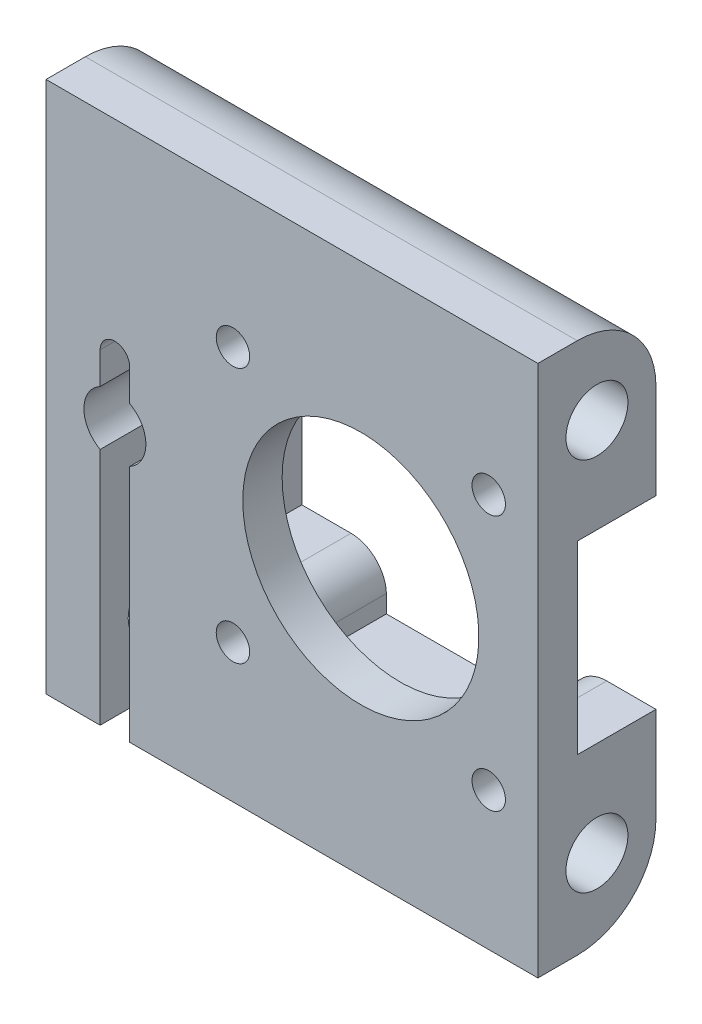
SolidWorks part; units mm, degrees
ref_plane "Front Plane" through (0, 0, 0) normal (0, 0, 1) x (1, 0, 0)
ref_plane "Top Plane" through (0, 0, 0) normal (0, 1, 0) x (1, 0, 0)
ref_plane "Right Plane" through (0, 0, 0) normal (1, 0, 0) x (0, 0, -1)
sketch "Sketch1" plane through (0, 0, 0) normal (0, 0, 1) x (1, 0, 0)
  line L1 (0, 0) -> (50, 0)
  line L2 (0, 0) -> (0, 54.105)
  line L3 (0, 54.105) -> (50, 54.105)
  line L4 (50, 0) -> (50, 54.105)
  dimension "D1" = 54.105
  dimension "D2" = 50
extrude "Boss-Extrude1" add sketch "Sketch1" along normal blind 12
sketch "Sketch2" plane through (0, 0, 0) normal (1, 0, 0) x (0, 0, -1)
  line L0 (-12, 27.0525) -> (0, 27.0525) construction
  line L1 (-12, 0) -> (-12, 54.105) construction
  line L2 (0, 0) -> (0, 54.105) construction
  circle A0 centre (-6, 46.105) radius 3.15
  circle A1 centre (-6, 8) radius 3.15
  dimension "D2" = 6.3
  dimension "D1" = 6
  dimension "D3" = 19.0525
extrude "Cut-Extrude1" cut sketch "Sketch2" along normal through all
fillet "Fillet1" radius 8 2 edges at (25, 0, 0) (25, 54.105, 0)
sketch "Sketch3" plane through (0, 0, 0) normal (0, 0, -1) x (-1, 0, 0)
  line L0 (-50, 27.0525) -> (0, 27.0525) construction
  line L1 (-50, 8) -> (-50, 46.105) construction
  line L2 (0, 46.105) -> (0, 8) construction
  line L3 (-8.5, 0) -> (-8.5, 24.2826)
  line L5 (-5.5, 33.0525) -> (-5.5, 29.8224)
  line L6 (0, 0) -> (-50, 0) construction
  line L7 (-8.5, 0) -> (-5.5, 0)
  line L8 (-8.5, 29.8224) -> (-8.5, 33.0525)
  line L9 (-5.5, 24.2826) -> (-5.5, 0)
  arc A0 (-8.5, 29.8224) -> (-8.5, 24.2826) centre (-7, 27.0525) ccw
  circle A1 centre (-32, 27.0525) radius 12
  circle A2 centre (-19, 40.0525) radius 1.7
  circle A3 centre (-19, 14.0525) radius 1.7
  arc A4 (-5.5, 24.2826) -> (-5.5, 29.8224) centre (-7, 27.0525) ccw
  arc A5 (-5.5, 33.0525) -> (-8.5, 33.0525) centre (-7, 33.0525) ccw
  circle A6 centre (-45, 14.0525) radius 1.7
  circle A7 centre (-45, 40.0525) radius 1.7
  dimension "D1" = 24
  dimension "D2" = 6.3
  dimension "D5" = 3.4
  dimension "D6" = 1.5
  dimension "D7" = 13
  dimension "D10" = 13
  dimension "D3" = 7
  dimension "D4" = 25
  dimension "D8" = 3
  dimension "D9" = 6
  dimension "D11" = 4
extrude "Cut-Extrude2" cut sketch "Sketch3" against normal through all
sketch "Sketch5" plane through (0, 0, 0) normal (0, 0, -1) x (-1, 0, 0)
  line L0 (-50, 27.0525) -> (-29.1332, 27.0525) construction
  line L1 (-19, 17.6525) -> (-14, 17.6525)
  line L2 (-50, 36.4525) -> (-50, 17.6525)
  line L4 (-14, 36.4525) -> (-14, 17.6525)
  line L5 (-50, 8) -> (-50, 46.105) construction
  line L7 (0, 46.105) -> (0, 8) construction
  line L8 (-41.4013, 41.7525) -> (-22.5987, 41.7525)
  line L9 (-22.5987, 41.7525) -> (-22.5987, 39.955)
  line L10 (-41.4013, 39.955) -> (-41.4013, 41.7525)
  line L11 (-45, 36.4525) -> (-50, 36.4525)
  line L12 (-19, 36.4525) -> (-14, 36.4525)
  line L13 (-45, 17.6525) -> (-50, 17.6525)
  line L14 (-41.4013, 14.15) -> (-41.4013, 12.3525)
  line L15 (-22.5987, 12.3525) -> (-22.5987, 14.15)
  line L16 (-41.4013, 12.3525) -> (-22.5987, 12.3525)
  arc A0 (-45, 36.4525) -> (-41.4013, 39.955) centre (-45, 40.0525) ccw
  arc A1 (-22.5987, 39.955) -> (-19, 36.4525) centre (-19, 40.0525) ccw
  circle A2 centre (-45, 40.0525) radius 1.7 construction
  circle A3 centre (-19, 40.0525) radius 1.7 construction
  arc A4 (-22.5987, 14.15) -> (-19, 17.6525) centre (-19, 14.0525) cw
  arc A5 (-45, 17.6525) -> (-41.4013, 14.15) centre (-45, 14.0525) cw
  dimension "D5" = 3.6
  dimension "D4" = 14
extrude "Cut-Extrude4" cut sketch "Sketch5" against normal offset from surface (8 mm away) 4 up to face at (43.3, 40.0525, 12)
sketch "Sketch4" plane through (0, 0, 0) normal (0, 0, -1) x (-1, 0, 0)
  circle A0 centre (-32, 27.0525) radius 6.7
  circle A1 centre (-32, 27.0525) radius 12 construction
  dimension "D1" = 13.4
extrude "Cut-Extrude3" [suppressed] cut sketch "Sketch4" against normal offset from surface (9 mm away) 3 up to face at (43.3, 40.0525, 12)
